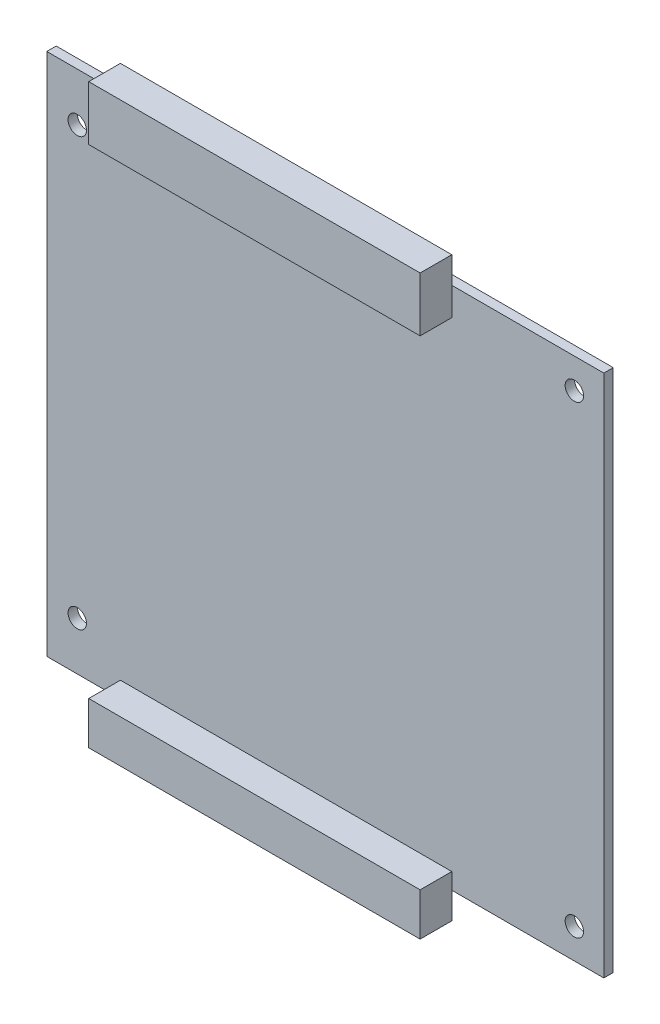
SolidWorks part; units mm, degrees
ref_plane "Front Plane" through (0, 0, 0) normal (0, 0, 1) x (1, 0, 0)
ref_plane "Top Plane" through (0, 0, 0) normal (0, 1, 0) x (1, 0, 0)
ref_plane "Right Plane" through (0, 0, 0) normal (1, 0, 0) x (0, 0, -1)
sketch "Sketch1" plane through (0, 0, 0) normal (0, 0, 1) x (1, 0, 0)
  line L1 (-48.0314, -45.1739) -> (48.0314, -45.1739)
  line L2 (-48.0314, -45.1739) -> (-48.0314, 45.1739)
  line L3 (-48.0314, 45.1739) -> (48.0314, 45.1739)
  line L4 (48.0314, -45.1739) -> (48.0314, 45.1739)
  line L5 (-48.0314, -45.1739) -> (48.0314, 45.1739) construction
  line L6 (-48.0314, 45.1739) -> (48.0314, -45.1739) construction
  point P0 (0, 0)
  dimension "D1" = 96.0628
  dimension "D2" = 90.3478
extrude "PCB" add sketch "Sketch1" along normal blind 1.6256
sketch "Sketch5" plane through (0, 0, 1.6256) normal (0, 0, 1) x (1, 0, 0)
  line L0 (-42.7736, 45.1739) -> (-42.7736, 36.83) construction
  line L1 (48.0314, 45.1739) -> (-48.0314, 45.1739) construction
  line L2 (-42.7736, 36.83) -> (-42.7736, -36.83) construction
  line L3 (-42.7736, -36.83) -> (-42.7736, -45.1739) construction
  line L4 (-48.0314, -45.1739) -> (48.0314, -45.1739) construction
  line L5 (48.0314, -45.1739) -> (48.0314, 45.1739) construction
  line L6 (42.9514, 45.1739) -> (42.9514, 40.005) construction
  line L7 (42.9514, 40.005) -> (42.9514, -40.005) construction
  line L8 (42.9514, -40.005) -> (42.9514, -45.1739) construction
  circle A0 centre (-42.7736, 36.83) radius 1.5875
  circle A1 centre (42.9514, 40.005) radius 1.5875
  circle A2 centre (42.9514, -40.005) radius 1.5875
  circle A3 centre (-42.7736, -36.83) radius 1.5875
  dimension "D5" = 3.175
  dimension "D1" = 73.66
  dimension "D2" = 90.805
  dimension "D3" = 80.01
  dimension "D4" = 5.08
extrude "PCB_Holes" cut sketch "Sketch5" against normal through all
sketch "Sketch2" plane through (0, 0, 1.6256) normal (0, 0, 1) x (1, 0, 0)
  line L0 (-48.0314, 45.1739) -> (-48.0314, -45.1739) construction
  line L1 (-43.6372, 30.5181) -> (-35.6616, 30.5181)
  line L2 (-43.6372, 30.5181) -> (-43.6372, -29.7053)
  line L3 (-43.6372, -29.7053) -> (-35.6616, -29.7053)
  line L4 (-35.6616, 30.5181) -> (-35.6616, -29.7053)
  line L5 (-48.0314, -45.1739) -> (48.0314, -45.1739) construction
  dimension "D1" = 60.2234
  dimension "D2" = 7.9756
  dimension "D3" = 4.3942
  dimension "D4" = 15.4686
extrude "PCI-104_Connector" [suppressed] add sketch "Sketch2" along normal blind 9.2964 and the other way offset from surface 10.9982
sketch "Sketch6" plane through (0, 0, 1.6256) normal (0, 0, 1) x (1, 0, 0)
  line L0 (-48.0314, -45.1739) -> (48.0314, -45.1739) construction
  line L1 (-35.3314, -42.3799) -> (21.8186, -42.3799)
  line L2 (-35.3314, -42.3799) -> (-35.3314, -49.7459)
  line L3 (-35.3314, -49.7459) -> (21.8186, -49.7459)
  line L4 (21.8186, -42.3799) -> (21.8186, -49.7459)
  line L5 (-48.0314, 45.1739) -> (-48.0314, -45.1739) construction
  line L6 (48.0314, 45.1739) -> (-48.0314, 45.1739) construction
  line L7 (-35.3314, 40.3479) -> (21.8186, 40.3479)
  line L8 (-35.3314, 40.3479) -> (-35.3314, 49.7459)
  line L9 (-35.3314, 49.7459) -> (21.8186, 49.7459)
  line L10 (21.8186, 40.3479) -> (21.8186, 49.7459)
  dimension "D1" = 7.366
  dimension "D2" = 4.572
  dimension "D3" = 57.15
  dimension "D4" = 12.7
  dimension "D5" = 9.398
  dimension "D7" = 12.7
  dimension "D8" = 4.572
extrude "PCB_Edge_Conns" add sketch "Sketch6" along normal blind 5.461
